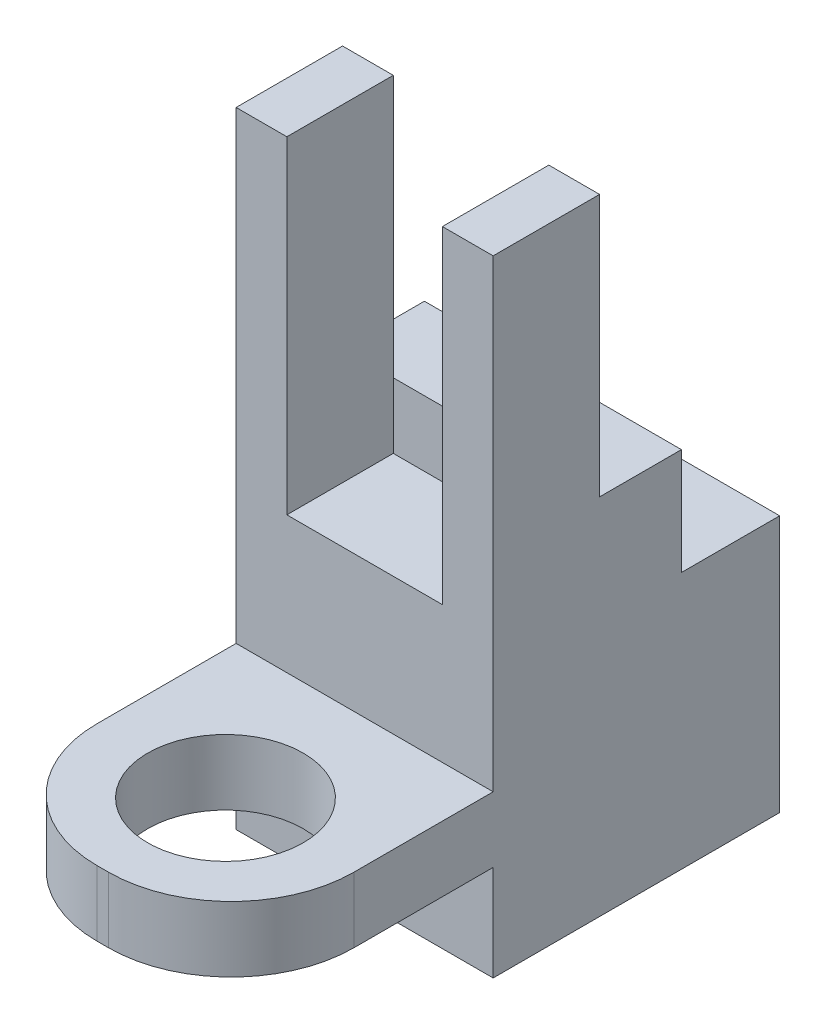
SolidWorks part; units mm, degrees
ref_plane "Front Plane" through (0, 0, 0) normal (0, 0, 1) x (1, 0, 0)
ref_plane "Top Plane" through (0, 0, 0) normal (0, 1, 0) x (1, 0, 0)
ref_plane "Right Plane" through (0, 0, 0) normal (1, 0, 0) x (0, 0, -1)
sketch "Sketch4" plane through (0, 0, 0) normal (0, 0, 1) x (1, 0, 0)
  line L0 (0, 82.063) -> (0, -112.4411) construction
  line L1 (-144.2959, 0) -> (145.5617, 0) construction
  line L2 (-12.7, 12.7) -> (-12.7, -12.7)
  line L3 (-15.7, 15.7) -> (15.7, 15.7)
  line L4 (-15.7, 15.7) -> (-15.7, -15.7)
  line L5 (-15.7, -15.7) -> (15.7, -15.7)
  line L6 (15.7, 15.7) -> (15.7, -15.7)
  line L7 (-12.7, -12.7) -> (12.7, -12.7)
  line L8 (12.7, 12.7) -> (12.7, -12.7)
  line L9 (-12.7, 12.7) -> (12.7, 12.7)
  dimension "D2" = 12.7
  dimension "D3" = 12.7
  dimension "D4" = 12.7
  dimension "D5" = 12.7
  dimension "D1" = 3
extrude "Boss-Extrude3" add sketch "Sketch4" along normal blind 30
sketch "Sketch5" plane through (0, 0, 30) normal (0, 0, 1) x (1, 0, 0)
  line L0 (-15.7, 15.7) -> (15.7, 15.7)
  line L1 (15.7, 15.7) -> (15.7, -15.7)
  line L2 (15.7, -15.7) -> (-15.7, -15.7)
  line L3 (-15.7, -15.7) -> (-15.7, 15.7)
extrude "Boss-Extrude4" add sketch "Sketch5" along normal blind 5
sketch "Sketch6" plane through (0, 0, 35) normal (0, 0, 1) x (1, 0, 0)
  line L0 (-14.6567, 0) -> (15.7, 0) construction
  line L1 (15.7, -15.7) -> (15.7, 15.7) construction
  line L2 (-15.7, 4) -> (15.7, 4)
  line L3 (-15.7, 15.7) -> (-15.7, -15.7) construction
  line L4 (15.7, 4) -> (15.7, -4)
  line L5 (15.7, -4) -> (-15.7, -4)
  line L6 (-15.7, -4) -> (-15.7, 4)
  dimension "D1" = 4
  dimension "D2" = 4
extrude "Boss-Extrude5" add sketch "Sketch6" along normal blind 5
sketch "Sketch7" plane through (0, -4, 0) normal (0, -1, 0) x (1, 0, 0)
  line L0 (-15.7, 40) -> (-15.7, 52)
  line L1 (-0.7, 67) -> (0.7, 67)
  line L2 (15.7, 52) -> (15.7, 40)
  line L3 (-15.7, 40) -> (15.7, 40) construction
  line L4 (15.7, 40) -> (-15.7, 40)
  line L5 (0, 0) -> (0, 92.3619) construction
  arc A0 (0.7, 67) -> (15.7, 52) centre (0.7, 52) cw
  arc A1 (-15.7, 52) -> (-0.7, 67) centre (-0.7, 52) cw
  point P9 (15.7, 67)
  point P12 (-15.7, 67)
  dimension "D3" = 15
  dimension "D1" = 27
  dimension "D2" = 31.4
extrude "Boss-Extrude6" add sketch "Sketch7" against normal blind 8
sketch "Sketch8" plane through (0, -4, 0) normal (0, -1, 0) x (1, 0, 0)
  line L0 (0, 67.4318) -> (0, -5.9603) construction
  line L1 (0.7, 67) -> (-0.7, 67) construction
  circle A0 centre (0, 52) radius 9.5
  dimension "D1" = 15
extrude "Boss-Extrude7" add sketch "Sketch8" along normal blind 8
mirror "Mirror1" about plane through (0, 0, 0) normal (0, 1, 0) of "Boss-Extrude7"
sketch "Sketch9" plane through (0, 15.7, 0) normal (0, 1, 0) x (1, 0, 0)
  line L1 (-15.7, -32) -> (15.7, -32)
  line L2 (-15.7, -35) -> (-15.7, 0) construction
  line L3 (15.7, -35) -> (15.7, 0) construction
  line L4 (0, 15.8647) -> (0, -78.6922) construction
  line L5 (0, -52) -> (31.7707, -52) construction
  line L6 (31.7707, -52) -> (-30.9902, -52) construction
  line L7 (-15.7, -32) -> (-15.7, -22)
  line L8 (-15.7, -22) -> (15.7, -22)
  line L9 (15.7, -22) -> (15.7, -32)
  dimension "D1" = 20
  dimension "D2" = 10
extrude "Boss-Extrude8" add sketch "Sketch9" along normal blind 5
sketch "Sketch10" plane through (0, 15.7, 0) normal (0, 1, 0) x (1, 0, 0)
  line L0 (-15.7, -22) -> (-15.7, -12)
  line L1 (-15.7, -22) -> (-15.7, 0) construction
  line L2 (-15.7, -12) -> (15.7, -12)
  line L3 (15.7, -22) -> (15.7, 0) construction
  line L4 (15.7, -12) -> (15.7, -22)
  line L5 (15.7, -22) -> (-15.7, -22)
  dimension "D1" = 10
extrude "Boss-Extrude9" add sketch "Sketch10" along normal blind 13
sketch "Sketch11" plane through (0, 20.7, 0) normal (0, 1, 0) x (1, 0, 0)
  line L0 (-15.7, -22) -> (-9.5, -22)
  line L1 (15.7, -22) -> (-15.7, -22) construction
  line L2 (-9.5, -22) -> (-9.5, -32)
  line L3 (-15.7, -32) -> (15.7, -32) construction
  line L4 (-9.5, -32) -> (-15.7, -32)
  line L5 (-15.7, -32) -> (-15.7, -22)
  line L6 (9.5, -22) -> (9.5, -32)
  line L7 (-15.7, -22) -> (15.7, -22) construction
  line L8 (-15.7, -32) -> (15.7, -32) construction
  line L9 (9.5, -32) -> (15.7, -32)
  line L10 (15.7, -32) -> (15.7, -22)
  line L11 (15.7, -32) -> (15.7, -22) construction
  line L12 (15.7, -22) -> (9.5, -22)
  dimension "D1" = 6.2
  dimension "D2" = 6.2
extrude "Boss-Extrude10" add sketch "Sketch11" along normal blind 40
sketch "Sketch12" plane through (0, 0, 32) normal (0, 0, 1) x (1, 0, 0)
  line L0 (-15.7, 60.7) -> (-9.5, 60.7)
  line L1 (-9.5, 60.7) -> (-9.5, 20.7)
  line L2 (-9.5, 20.7) -> (9.5, 20.7)
  line L3 (9.5, 20.7) -> (9.5, 60.7)
  line L4 (9.5, 60.7) -> (15.7, 60.7)
  line L5 (15.7, 60.7) -> (15.7, 15.7)
  line L6 (15.7, 15.7) -> (-15.7, 15.7)
  line L7 (-15.7, 15.7) -> (-15.7, 60.7)
extrude "Boss-Extrude11" add sketch "Sketch12" along normal blind 3
extrude "Cut-Extrude1" cut sketch "Sketch8<2>" against normal blind 24 from offset 8
sketch "Sketch8<2>" plane through (0, -4, 0) normal (0, -1, 0) x (1, 0, 0) same geometry as "Sketch8"
